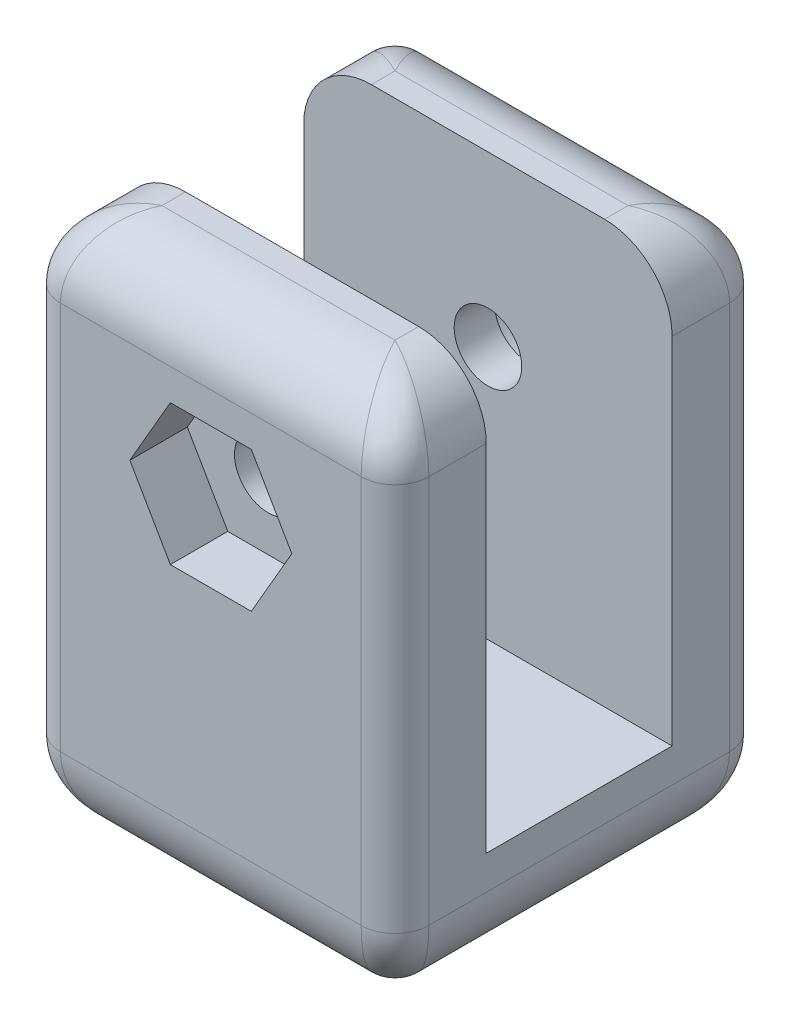
SolidWorks part; units mm, degrees
ref_plane "Alzado" through (0, 0, 0) normal (0, 0, 1) x (1, 0, 0)
ref_plane "Planta" through (0, 0, 0) normal (0, 1, 0) x (1, 0, 0)
ref_plane "Vista lateral" through (0, 0, 0) normal (1, 0, 0) x (0, 0, -1)
sketch "Croquis1" plane through (0, 0, 0) normal (1, 0, 0) x (0, 0, -1)
  line L1 (0, 0) -> (-21.8, 0)
  line L2 (0, 0) -> (0, -7)
  line L3 (0, -7) -> (-21.8, -7)
  line L4 (-21.8, 0) -> (-21.8, -7)
  dimension "D1" = 21.8
  dimension "D2" = 7
extrude "Saliente-Extruir1" add sketch "Croquis1" along normal blind 21.8 contours L2 L3 L4 L1
fillet "Redondeo3" radius 5 4 edges at (21.8, -7, 10.9) (10.9, -7, 0) (0, -7, 10.9) (10.9, -7, 21.8)
ref_plane "Plano1" through (0, 0, 10.9) normal (0, 0, 1) x (1, 0, 0)
sketch "Croquis5" plane through (0, 0, 10.9) normal (0, 0, 1) x (1, 0, 0)
  line L0 (10.9, 25) -> (10.9, 15) construction
  line L1 (0, 0) -> (21.8, 0)
  line L2 (0, 0) -> (0, 25)
  line L3 (0, 25) -> (21.8, 25)
  line L4 (21.8, 0) -> (21.8, 25)
  circle A0 centre (10.9, 15) radius 2
  point P4 (0, 0)
  point P8 (0, 0)
  point P9 (0, 0)
  dimension "D3" = 4
  dimension "D1" = 25
  dimension "D2" = 10
  dimension "D4" = 21.8
extrude "Saliente-Extruir2" add sketch "Croquis5" along normal mid plane 21.8
sketch "Croquis6" plane through (0, 0, 0) normal (-1, 0, 0) x (0, 0, 1)
  line L0 (10.9, 25) -> (10.9, 5.0643) construction
  line L1 (21.8, 25) -> (0, 25) construction
  line L2 (10.9, 5.0643) -> (5.4, 5.0643) construction
  line L3 (10.9, 5.0643) -> (16.4, 5.0643) construction
  line L5 (5.4, 25) -> (16.4, 25)
  line L6 (5.4, 25) -> (5.4, 0)
  line L7 (5.4, 0) -> (16.4, 0)
  line L8 (16.4, 25) -> (16.4, 0)
  dimension "D1" = 5.5
  dimension "D2" = 5.5
extrude "Cortar-Extruir1" cut sketch "Croquis6" against normal up to next
sketch "Croquis7" plane through (0, 0, 21.8) normal (0, 0, 1) x (1, 0, 0)
  line L0 (21.8, 25) -> (0, 25) construction
  line L1 (15.692, 15) -> (13.296, 19.15)
  line L2 (13.296, 19.15) -> (8.504, 19.15)
  line L3 (8.504, 19.15) -> (6.108, 15)
  line L4 (6.108, 15) -> (8.504, 10.85)
  line L5 (8.504, 10.85) -> (13.296, 10.85)
  line L6 (13.296, 10.85) -> (15.692, 15)
  circle A0 centre (10.9, 15) radius 4.15 construction
  dimension "D1" = 8.3
extrude "Cortar-Extruir2" cut sketch "Croquis7" against normal blind 3.4
sketch "Croquis8" plane through (0, 0, 0) normal (0, 0, -1) x (-1, 0, 0)
  circle A0 centre (-10.9, 15) radius 3.5
  dimension "D1" = 7
extrude "Cortar-Extruir3" cut sketch "Croquis8" against normal blind 3
sketch "Croquis12" plane through (21.8, 0, 0) normal (1, 0, 0) x (0, 0, -1)
  line L0 (-10.9, 17) -> (-10.9, -7) construction
  line L1 (-5, -7) -> (-16.8, -7) construction
fillet "Redondeo8" radius 4 6 edges at (10.9, 25, 0) (0, 25, 2.7) (21.8, 25, 2.7) (0, 25, 19.1) (21.8, 25, 19.1) (10.9, 25, 21.8)
fillet "Redondeo9" radius 2 12 edges at (20.6284, 23.8284, 1.1716) (20.3355, -5.5355, 1.4645) (1.1716, 23.8284, 1.1716) (1.4645, -5.5355, 1.4645) (20.6284, 23.8284, 20.6284) (20.3355, -5.5355, 20.3355) (1.1716, 23.8284, 20.6284) (1.4645, -5.5355, 20.3355) (21.8, 9.5, 0) (0, 9.5, 0) (21.8, 9.5, 21.8) (0, 9.5, 21.8)
